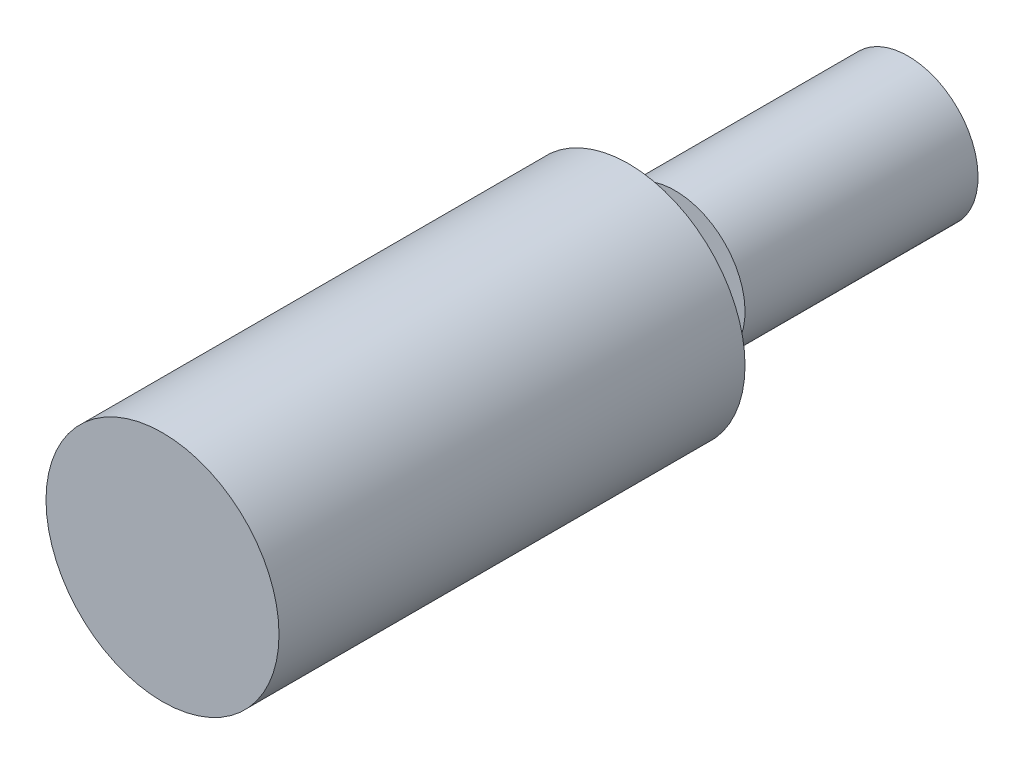
SolidWorks part; units mm, degrees
ref_plane "1" through (0, 0, 0) normal (0, 0, 1) x (1, 0, 0)
ref_plane "2" through (0, 0, 0) normal (0, 1, 0) x (1, 0, 0)
ref_plane "3" through (0, 0, 0) normal (1, 0, 0) x (0, 0, -1)
ref_plane "Front Plane" through (0, 0, 0) normal (0, -1, 0) x (1, 0, 0)
ref_plane "Right Plane" through (0, 0, 0) normal (1, 0, 0) x (0, 1, 0)
ref_plane "Top Plane" through (0, 0, 0) normal (0, 0, 1) x (1, 0, 0)
ref_axis "Axis1" through (0, 0, 50.7014) along (0, 0, -1)
sketch "Sketch1" plane through (0, 0, 0) normal (0, -1, 0) x (1, 0, 0)
  line L0 (0, 44.6812) -> (0, -7.0401) construction
  line L1 (0, 10) -> (2.5, 10)
  line L2 (2.5, 10) -> (2.5, 0)
  line L3 (2.5, 0) -> (1, 0)
  line L4 (0, -6) -> (1.5, -6)
  line L5 (1.5, -6) -> (1.5, -1)
  line L6 (1.5, -1) -> (1, -1)
  line L7 (1, -1) -> (1, 0)
  line L8 (0, -6) -> (0, 10)
  dimension "D1" = 5
  dimension "D2" = 6
  dimension "D3" = 3
  dimension "D4" = 10
  dimension "D5" = 1
  dimension "D6" = 2
revolve "Revolve1" add sketch "Sketch1" angle 360 about L0
